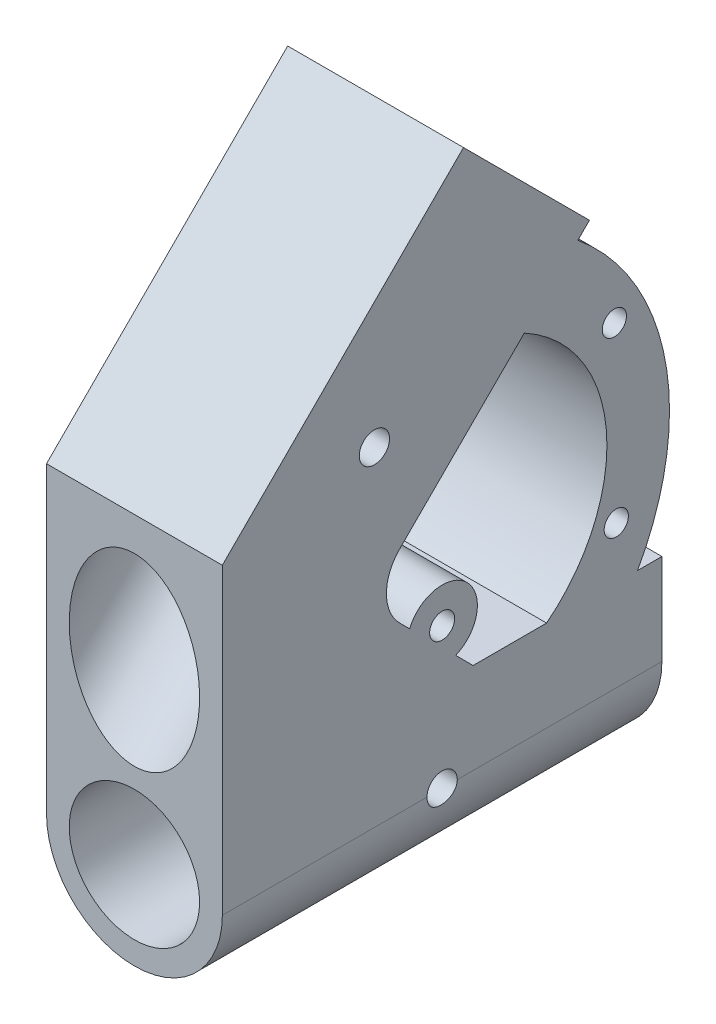
SolidWorks part; units mm, degrees
ref_plane "Alzado" through (0, 0, 0) normal (0, 0, 1) x (1, 0, 0)
ref_plane "Planta" through (0, 0, 0) normal (0, 1, 0) x (1, 0, 0)
ref_plane "Vista lateral" through (0, 0, 0) normal (1, 0, 0) x (0, 0, -1)
sketch "Croquis1" plane through (0, 0, 0) normal (0, 0, 1) x (1, 0, 0)
  line L0 (0, 0) -> (0, -10) construction
  line L4 (0, 0) -> (0, 12) construction
  line L5 (-11.6, 12) -> (11.6, 12)
  line L6 (-11.6, 12) -> (-11.6, 0)
  line L7 (11.6, 12) -> (11.6, 0)
  circle A0 centre (0, 0) radius 8.6
  arc A2 (-11.6, 0) -> (11.6, 0) centre (0, 0) ccw
  point P8 (0, -10)
  point P9 (0, 12)
  dimension "D1" = 17.2
  dimension "D2" = 3
  dimension "D4" = 12
extrude "Saliente-Extruir1" add sketch "Croquis1" against normal mid plane 58
sketch "Croquis2" plane through (0, 0, 0) normal (1, 0, 0) x (0, 0, -1)
  line L0 (-29, 12) -> (-29, 40)
  line L1 (-29, 40) -> (2.8198, 71.8198)
  line L2 (2.8198, 71.8198) -> (19.4368, 55.2028)
  line L3 (29, 12) -> (-29, 12) construction
  line L4 (-29, 12) -> (4.0901, 12)
  line L5 (19.4368, 55.2028) -> (-5.5953, 30.1707)
  line L6 (-5.5953, 21.6854) -> (4.0901, 12)
  arc A0 (-5.5953, 21.6854) -> (-5.5953, 30.1707) centre (-1.3527, 25.928) cw
  dimension "D4" = 135
  dimension "D5" = 6
  dimension "D1" = 28
  dimension "D2" = 45
  dimension "D3" = 23.5
extrude "Saliente-Extruir2" add sketch "Croquis2" along normal mid plane 23.2
ref_plane "Plano1" through (0, 37.3198, -37.3198) normal (0, 0.7071, -0.7071) x (-1, 0, 0)
sketch "Croquis3" plane through (0, 37.3198, -37.3198) normal (0, 0.7071, -0.7071) x (1, 0, 0)
  line L0 (0, -48.7904) -> (0, -25.2904) construction
  line L1 (11.6, -48.7904) -> (-11.6, -48.7904) construction
  line L4 (11.6, -25.2904) -> (-11.6, -25.2904) construction
  circle A0 centre (0, -37.0404) radius 8.6
  dimension "D1" = 17.2
extrude "Cortar-Extruir1" cut sketch "Croquis3" against normal blind 73
sketch "Croquis4" plane through (0, 0, 0) normal (1, 0, 0) x (0, 0, -1)
  line L0 (-5.5953, 30.1707) -> (19.4368, 55.2028) construction
  line L1 (29, 12) -> (4.0901, 12) construction
  line L2 (10.8367, 46.6027) -> (17.9078, 53.6738)
  line L3 (13.7825, 12) -> (25.7825, 12)
  line L4 (19.4368, 55.2028) -> (2.8198, 71.8198) construction
  line L5 (29, 0) -> (29, 12) construction
  arc A0 (10.8367, 46.6027) -> (13.7825, 12) centre (1, 28.3386) cw
  arc A1 (17.9078, 53.6738) -> (25.7825, 12) centre (-3, 28.1421) cw
  dimension "D3" = 33
  dimension "D4" = 4
  dimension "D5" = 35
  dimension "D6" = 32
  dimension "D1" = 10
  dimension "D2" = 12
extrude "Saliente-Extruir3" add sketch "Croquis4" along normal mid plane 23.2
sketch "Croquis5" plane through (0, 0, 0) normal (1, 0, 0) x (0, 0, -1)
  circle A0 centre (0, 18.5926) radius 4.65
  circle A1 centre (0, 18.5926) radius 1.65
  dimension "D1" = 3.3
  dimension "D2" = 3
extrude "Saliente-Extruir4" add sketch "Croquis5" along normal mid plane 23.2
sketch "Croquis6" plane through (0, 0, 0) normal (1, 0, 0) x (0, 0, -1)
  circle A0 centre (22.7263, 41.8254) radius 1.6
  circle A1 centre (22.98, 18.8454) radius 1.6
  circle A2 centre (0, 18.5926) radius 1.65 construction
  dimension "D1" = 3.2
  dimension "D2" = 22.98
  dimension "D3" = 32.5
  dimension "D4" = 22.98
extrude "Cortar-Extruir2" cut sketch "Croquis6" against normal mid plane 30 contours A0 | A1
sketch "Croquis7" plane through (0, 0, 0) normal (1, 0, 0) x (0, 0, -1)
  line L0 (11.1283, 63.5113) -> (-29, 23.383) construction
  line L1 (19.4368, 55.2028) -> (2.8198, 71.8198) construction
  line L2 (-29, 40) -> (-29, 0) construction
  circle A0 centre (0, 0) radius 2
  circle A2 centre (-8.9358, 43.4471) radius 2
  dimension "D1" = 4
extrude "Cortar-Extruir3" cut sketch "Croquis7" against normal mid plane 53
